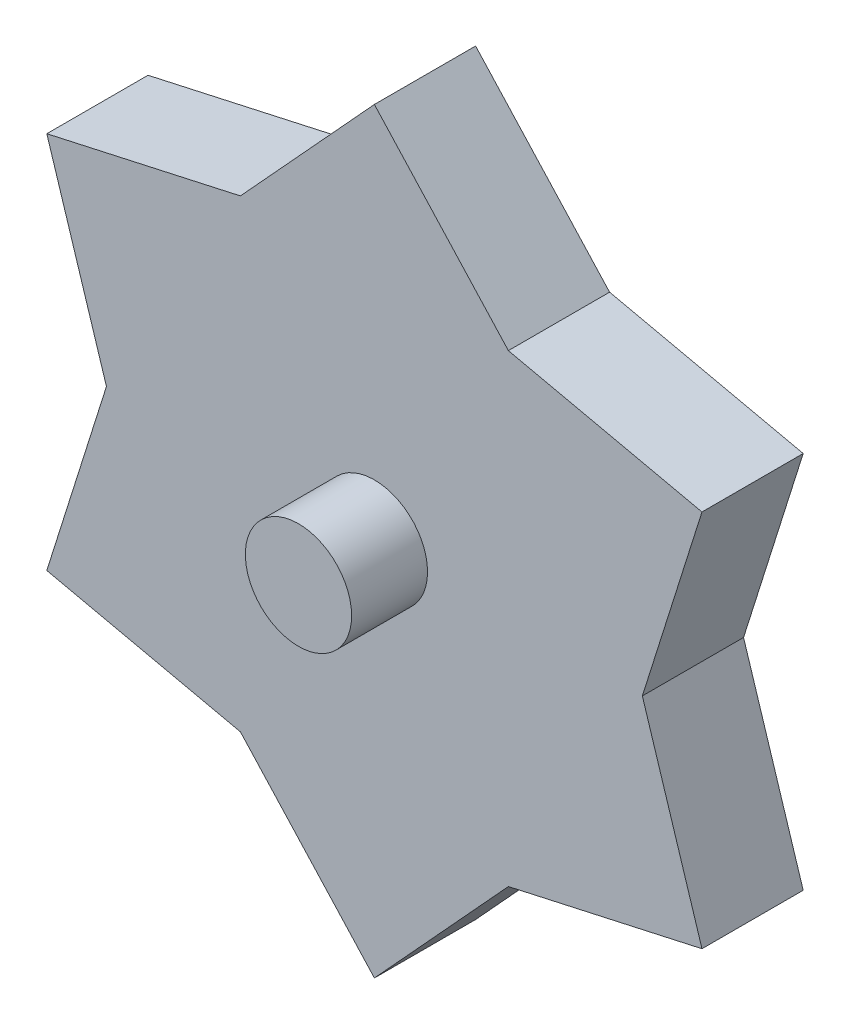
SolidWorks part; units mm, degrees
ref_plane "Front Plane" through (0, 0, 0) normal (0, 0, 1) x (1, 0, 0)
ref_plane "Top Plane" through (0, 0, 0) normal (0, 1, 0) x (1, 0, 0)
ref_plane "Right Plane" through (0, 0, 0) normal (1, 0, 0) x (0, 0, -1)
sketch "Sketch1" plane through (0, 0, 0) normal (0, 0, 1) x (1, 0, 0)
  line L0 (0, 7.4749) -> (0, -5.749) construction
  line L1 (-3.7233, 3.4117) -> (0, 7.4749)
  line L2 (0, 7.4749) -> (3.7233, 3.4117)
  line L3 (1.093, 4.9303) -> (6.4735, 3.7375)
  line L4 (6.4735, 3.7375) -> (4.8163, -1.5186)
  line L5 (4.8163, 1.5186) -> (6.4735, -3.7375)
  line L6 (6.4735, -3.7375) -> (1.093, -4.9303)
  line L7 (3.7233, -3.4117) -> (0, -7.4749)
  line L8 (0, -7.4749) -> (-3.7233, -3.4117)
  line L9 (-1.093, -4.9303) -> (-6.4735, -3.7375)
  line L10 (-6.4735, -3.7375) -> (-4.8163, 1.5186)
  line L11 (-4.8163, -1.5186) -> (-6.4735, 3.7375)
  line L12 (-6.4735, 3.7375) -> (-1.093, 4.9303)
  circle A0 centre (0, 0) radius 1.05
  circle A1 centre (0, 0) radius 5.05
  point P26 (0, 0)
  dimension "D1" = 2.1
  dimension "D3" = 85
  dimension "D4" = 42.5
  dimension "D2" = 4
  dimension "D5" = 6
extrude "Boss-Extrude1" add sketch "Sketch1" against normal blind 2 contours A1 A0 | A1 L1 L12 L11 L10 | L2 L0 A1 L3 | L0 L1 L12 A1 | A1 L12 L1 | A1 L2 L3 | A1 L5 L4 L3 L2 | L0 A1 A0 | A1 L11 L10 L9 L8 | A1 L10 L11 | A1 L8 L9 | A1 L9 L8 L7 L6 | A1 L6 L7 | A1 L7 L6 L5 L4 | A1 L4 L5 | A0 region at (0.8737, 5.7347, 0) region at (-0.8737, 5.7347, 0) region at (2.22, 0, 0) region at (-2.22, 0, 0) region at (-2.5502, 4.4171, 0) region at (-4.9664, 2.8673, 0) region at (4.9664, 2.8673, 0) region at (2.5502, 4.4171, 0) region at (-5.1004, 0, 0) region at (-4.9664, -2.8673, 0) region at (5.1004, 0, 0) region at (4.9664, -2.8673, 0) region at (0.5563, -5.0799, 0) region at (-2.5502, -4.4171, 0) region at (2.5502, -4.4171, 0)
extrude "Boss-Extrude2" add sketch "Sketch1<4>" along normal blind 1.5 contours A0 L0 | L0 A0 region at (0.4456, 0, 0) region at (-0.4456, 0, 0)
sketch "Sketch1<4>" plane through (0, 0, 0) normal (0, 0, 1) x (1, 0, 0) same geometry as "Sketch1"
